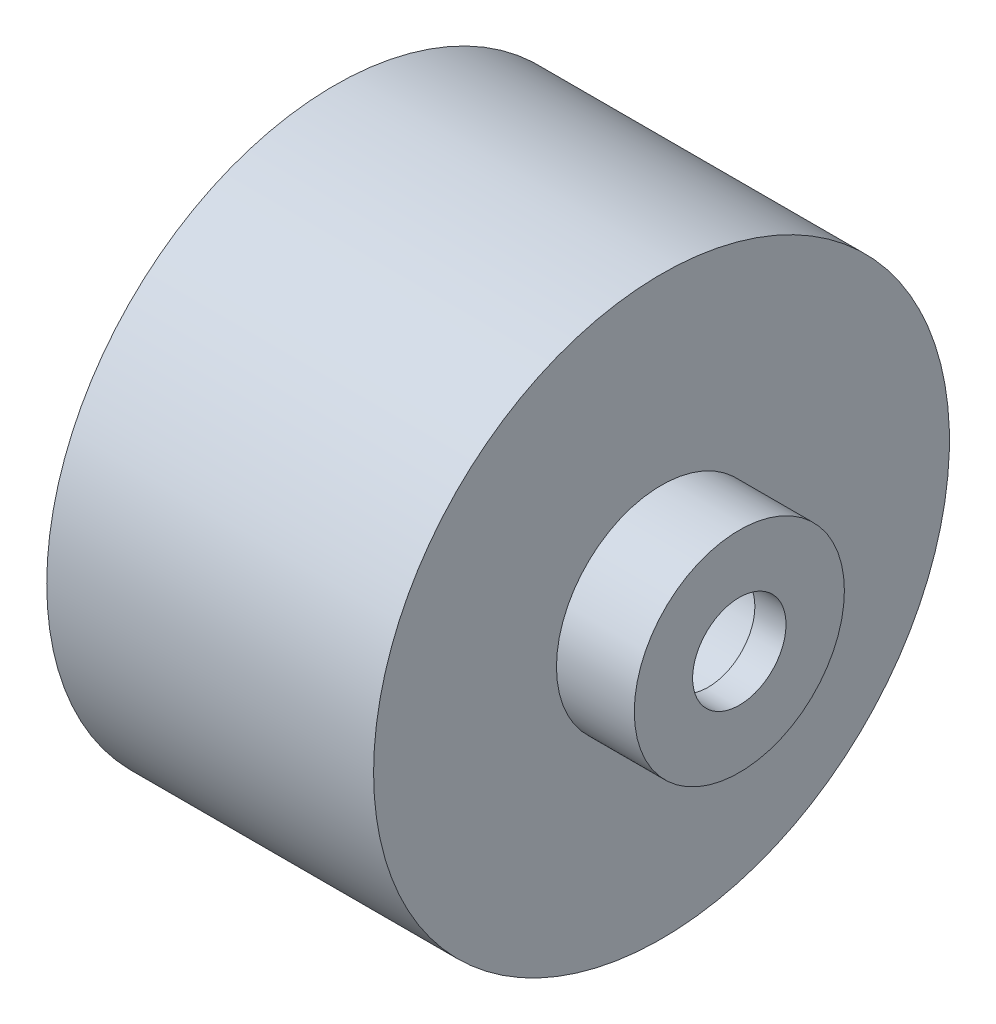
SolidWorks part; units mm, degrees
material "ABS"
ref_plane "Front Plane" through (0, 0, 0) normal (0, 0, 1) x (1, 0, 0)
ref_plane "Top Plane" through (0, 0, 0) normal (0, 1, 0) x (1, 0, 0)
ref_plane "Right Plane" through (0, 0, 0) normal (1, 0, 0) x (0, 0, -1)
sketch "Sketch1" plane through (0, 0, 0) normal (1, 0, 0) x (0, 0, -1)
  circle A0 centre (0, 0) radius 18.5
  dimension "D1" = 37
extrude "Boss-Extrude1" add sketch "Sketch1" along normal blind 21
sketch "Sketch2" plane through (21, 0, 0) normal (1, 0, 0) x (0, 0, -1)
  circle A0 centre (0, 0) radius 6.75
  dimension "D1" = 13.5
extrude "Boss-Extrude2" add sketch "Sketch2" along normal blind 5
shell "Shell1" thickness 2 removed face at (0, 0, -18.5)
sketch "Sketch3" plane through (26, 0, 0) normal (1, 0, 0) x (0, 0, -1)
  circle A0 centre (0, 0) radius 3
  dimension "D1" = 6
extrude "Cut-Extrude1" cut sketch "Sketch3" against normal blind 5
ref_axis "Axis1" through (21, 0, 0) along (-1, 0, 0)
